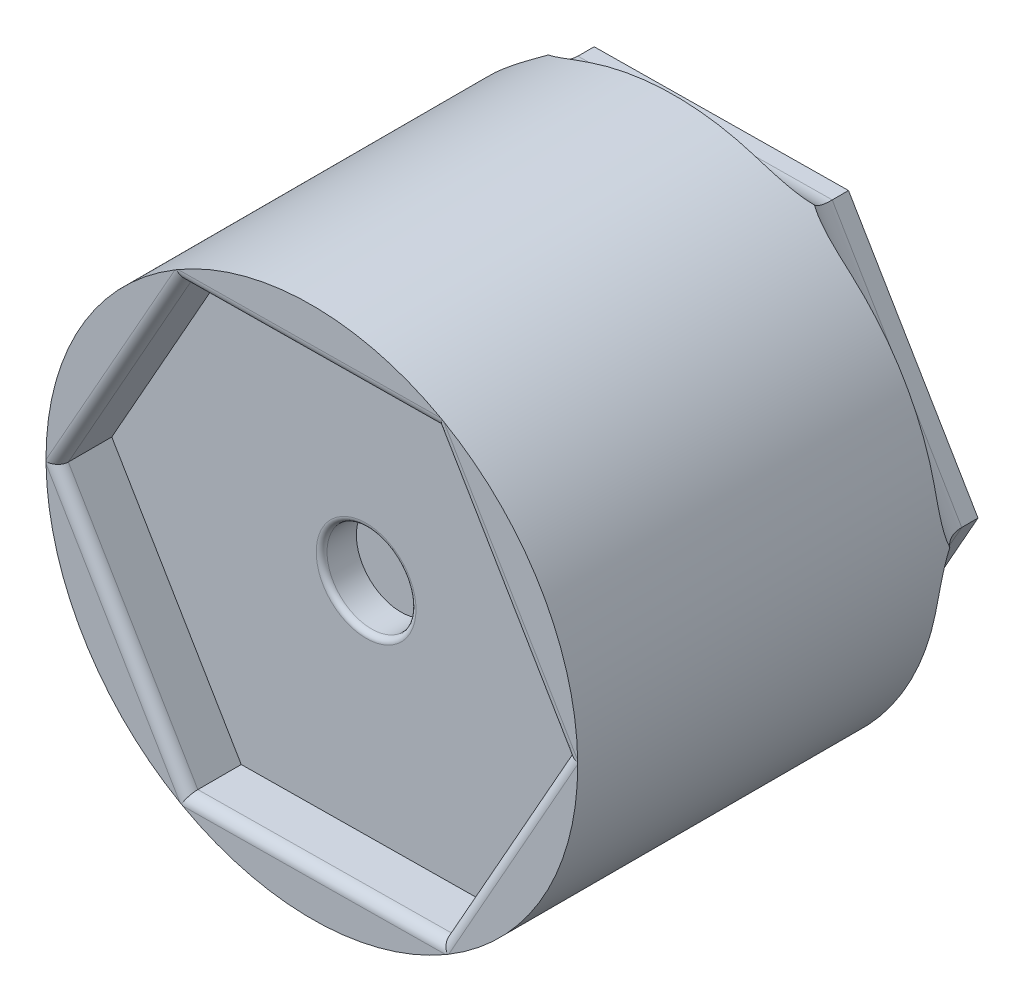
SolidWorks part; units mm, degrees
ref_plane "Front Plane" through (0, 0, 0) normal (1, 0, 0) x (0, 1, 0)
ref_plane "Top Plane" through (0, 0, 0) normal (0, 0, 1) x (0, 1, 0)
ref_plane "Right Plane" through (0, 0, 0) normal (0, 1, 0) x (-1, 0, 0)
sketch "Sketch1" plane through (0, 0, 0) normal (0, 0, 1) x (0, 1, 0)
  line L1 (20.1756, 11.9331) -> (-0.2466, 23.4391)
  line L2 (-0.2466, 23.4391) -> (-20.4222, 11.506)
  line L3 (-20.4222, 11.506) -> (-20.1756, -11.9331)
  line L4 (-20.1756, -11.9331) -> (0.2466, -23.4391)
  line L5 (0.2466, -23.4391) -> (20.4222, -11.506)
  line L6 (20.4222, -11.506) -> (20.1756, 11.9331)
  circle A0 centre (0, 0) radius 20.3 construction
extrude "HEX Feet" add sketch "Sketch1" along normal blind 4.5
sketch "Sketch3" plane through (0, 0, 4.5) normal (0, 0, 1) x (1, 0, 0)
  circle A0 centre (0, 0) radius 24.5
  dimension "D1" = 49
extrude "Circle Main Body" add sketch "Sketch3" along normal blind 33.45
sketch "Sketch4" plane through (0, 0, 37.95) normal (0, 0, 1) x (1, 0, 0)
  line L1 (11.506, 20.4222) -> (-11.9331, 20.1756)
  line L2 (-11.9331, 20.1756) -> (-23.4391, -0.2466)
  line L3 (-23.4391, -0.2466) -> (-11.506, -20.4222)
  line L4 (-11.506, -20.4222) -> (11.9331, -20.1756)
  line L5 (11.9331, -20.1756) -> (23.4391, 0.2466)
  line L6 (23.4391, 0.2466) -> (11.506, 20.4222)
  circle A0 centre (0, 0) radius 20.3 construction
extrude "TOP HEX Slot" cut sketch "Sketch4" against normal blind 5
fillet "Bottom hex chamf" radius 3 6 edges at (0.2136, -20.2989, 4.5) (17.6861, -9.9645, 4.5) (17.4726, 10.3344, 4.5) (-0.2136, 20.2989, 4.5) (-17.4726, -10.3344, 4.5) (-17.6861, 9.9645, 4.5)
fillet "Fillet2" radius 1 6 edges at (-17.6861, 9.9645, 37.95) (-17.4726, -10.3344, 37.95) (-0.2136, 20.2989, 37.95) (17.4726, 10.3344, 37.95) (17.6861, -9.9645, 37.95) (0.2136, -20.2989, 37.95)
sketch "Sketch5" plane through (0, 0, 32.95) normal (0, 0, 1) x (1, 0, 0)
  circle A0 centre (0, 0) radius 4.1
  dimension "D1" = 8.2
extrude "Cut-Extrude1" cut sketch "Sketch5" against normal blind 3.2
fillet "Fillet3" radius 0.5 1 edges at (4.1, 0, 32.95)
